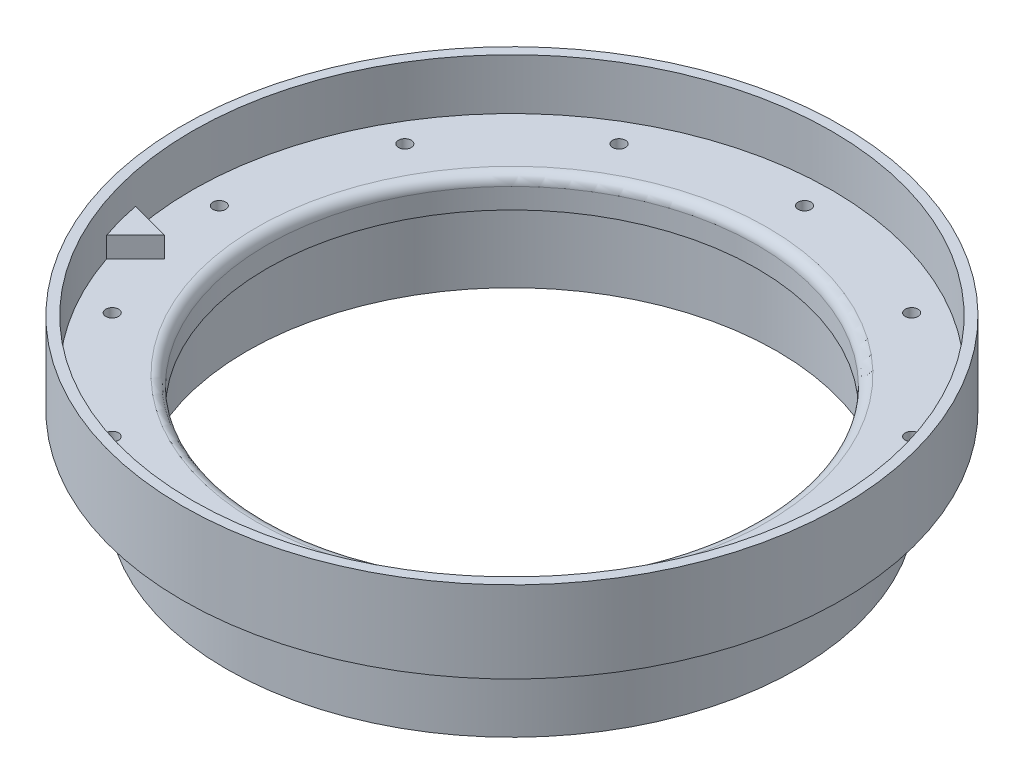
SolidWorks part; units mm, degrees
material "6061-T6 (SS)"
ref_plane "Front Plane" through (0, 0, 0) normal (0, 0, 1) x (1, 0, 0)
ref_plane "Top Plane" through (0, 0, 0) normal (0, 1, 0) x (1, 0, 0)
ref_plane "Right Plane" through (0, 0, 0) normal (1, 0, 0) x (0, 0, -1)
ref_axis "Axis1" through (0, 55, 0) along (0, -1, 0)
sketch "Cross Section" plane through (0, 0, 0) normal (0, 0, 1) x (1, 0, 0)
  line L0 (-38.1508, 0) -> (-38.1508, -3.175)
  line L1 (-38.1508, -3.175) -> (-41.275, -3.175)
  line L2 (-41.275, -3.175) -> (-41.275, -15.875)
  line L4 (0, -15.875) -> (-38.1, -15.875) construction
  line L5 (-44.45, -15.875) -> (-44.45, -3.175)
  line L6 (-44.45, -3.175) -> (-51.308, -3.175)
  line L7 (-51.308, -3.175) -> (-51.308, 9.525)
  line L8 (-51.308, 9.525) -> (-49.784, 9.525)
  line L9 (-49.784, 9.525) -> (-49.784, 1.5875)
  line L11 (-38.1508, 0) -> (0, 0) construction
  line L13 (-44.45, -15.875) -> (-41.275, -15.875)
  line L14 (-49.784, 1.5875) -> (-49.784, 3.175) construction
  line L15 (-39.7383, 1.5875) -> (-49.784, 1.5875)
  arc A0 (-39.7383, 1.5875) -> (-38.1508, 0) centre (-39.7383, 0) cw
  dimension "D2" = 1.5875
  dimension "D1" = 3.1242
  dimension "D3" = 3.175
  dimension "D5" = 6.858
  dimension "D6" = 12.7
  dimension "D9" = 3.175
  dimension "D4" = 1.5875
  dimension "D7" = 38.1508
revolve "Main" add sketch "Cross Section" angle 360 about axis through (0, 55, 0) along (0, -1, 0)
sketch "Hole Location" plane through (0, 0, 0) normal (0, 1, 0) x (1, 0, 0)
  line L0 (0, 0) -> (-45.5549, 0) construction
  circle A0 centre (0, 0) radius 45.5549 construction
  dimension "D1" = 91.1098
hole_wizard "#3-48 Tapped Hole1" positions "Sketch1" profile "Sketch2" tap size "#3-48" standard "ANSI Inch" end condition through all
sketch "Sketch1" plane through (0, 1.5875, 0) normal (0, 1, 0) x (1, 0, 0)
  point P0 (-45.5549, 0)
sketch "Sketch2" plane through (-45.5549, 1.5875, 0) normal (1, 0, 0) x (0, 0, 1)
  line L0 (0, 0) -> (0, 17.4625)
  line L1 (0, 17.4625) -> (0.9969, 17.4625)
  line L2 (0.9969, 17.4625) -> (0.9969, 0)
  line L5 (0.9969, 0) -> (0, 0)
  line L11 (0, -6.35) -> (0, 107.95) construction
  dimension "Thru Tap Drill Dia." = 1.9939
  dimension "Thru Tap Drill Depth" = 17.4625
cosmetic thread "Hole Thread1" parameters "D2"=2.5146
pattern_circular "CirPattern1" count 12 over 360 of "#3-48 Tapped Hole1"
sketch "Sketch3" plane through (0, 1.5875, 0) normal (0, 1, 0) x (1, 0, 0)
  line L0 (0, 0) -> (-48.0877, -12.885) construction
  line L1 (0, 0) -> (-45.5549, 0) construction
  line L2 (-47.168, -15.9256) -> (-42.6779, -11.4355)
  line L3 (-42.6779, -11.4355) -> (-48.8115, -9.792)
  circle A0 centre (0, 0) radius 49.784 construction
  circle A1 centre (0, 0) radius 49.784 construction
  arc A2 (-47.168, -15.9256) -> (-48.8115, -9.792) centre (0, 0) cw
  dimension "D1" = 15
  dimension "D2" = 60
  dimension "D3" = 6.35
extrude "Boss-Extrude1" add sketch "Sketch3" along normal blind 3.175
equation "\"D1@Hole Location\"=\"TANK DIAMETER@Cryo Tank.Assembly\"+\"GASKET SEAT THICKNESS@Cryo Tank.Assembly\"+\"LINER THICKNESS@Cryo Tank.Assembly\"+\"SHRINK FIT DELTA@Cryo Tank.Assembly\""
equation "\"D1@Cross Section\"=\"LINER THICKNESS@Cryo Tank.Assembly\"-0.002"
equation "\"D3@Cross Section\"=\"ALUMINUM LAP THICKNESS@Cryo Tank.Assembly\""
equation "\"D5@Cross Section\"=2*\"CF THICKNESS@Cryo Tank.Assembly\"+\"NOMEX THICKNESS@Cryo Tank.Assembly\""
equation "\"D7@Cross Section\"=\"TANK DIAMETER@Cryo Tank.Assembly\"/2+0.002"
